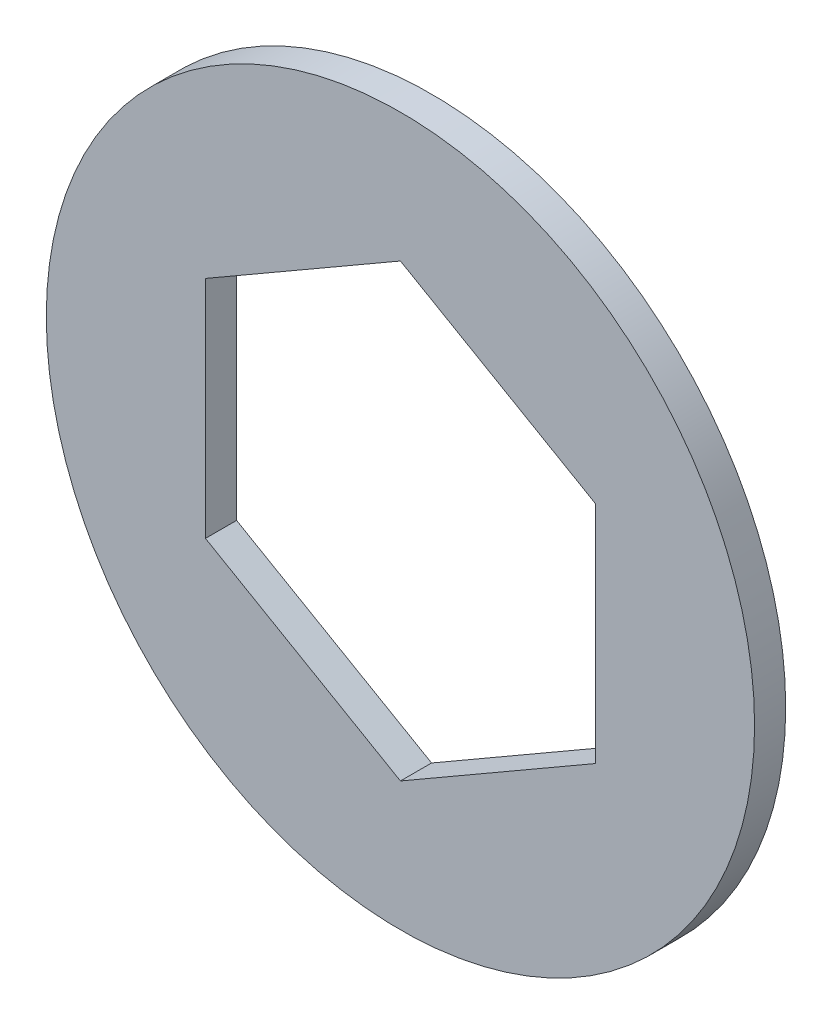
SolidWorks part; units mm, degrees
ref_plane "Plan de face" through (0, 0, 0) normal (0, 0, 1) x (1, 0, 0)
ref_plane "Plan de dessus" through (0, 0, 0) normal (0, 1, 0) x (1, 0, 0)
ref_plane "Plan de droite" through (0, 0, 0) normal (1, 0, 0) x (0, 0, -1)
sketch "Esquisse1" plane through (0, 0, 0) normal (0, 0, 1) x (1, 0, 0)
  line L1 (0, 28.9252) -> (-25.05, 14.4626)
  line L2 (-25.05, 14.4626) -> (-25.05, -14.4626)
  line L3 (-25.05, -14.4626) -> (0, -28.9252)
  line L4 (0, -28.9252) -> (25.05, -14.4626)
  line L5 (25.05, -14.4626) -> (25.05, 14.4626)
  line L6 (25.05, 14.4626) -> (0, 28.9252)
  circle A0 centre (0, 0) radius 45.5
  circle A1 centre (0, 0) radius 25.05 construction
  dimension "D1" = 91
  dimension "36" = 50.1
extrude "Boss.-Extru.1" add sketch "Esquisse1" along normal blind 4
ref_axis "Axis1" through (0, 0, 6.3) along (0, 0, -1)
